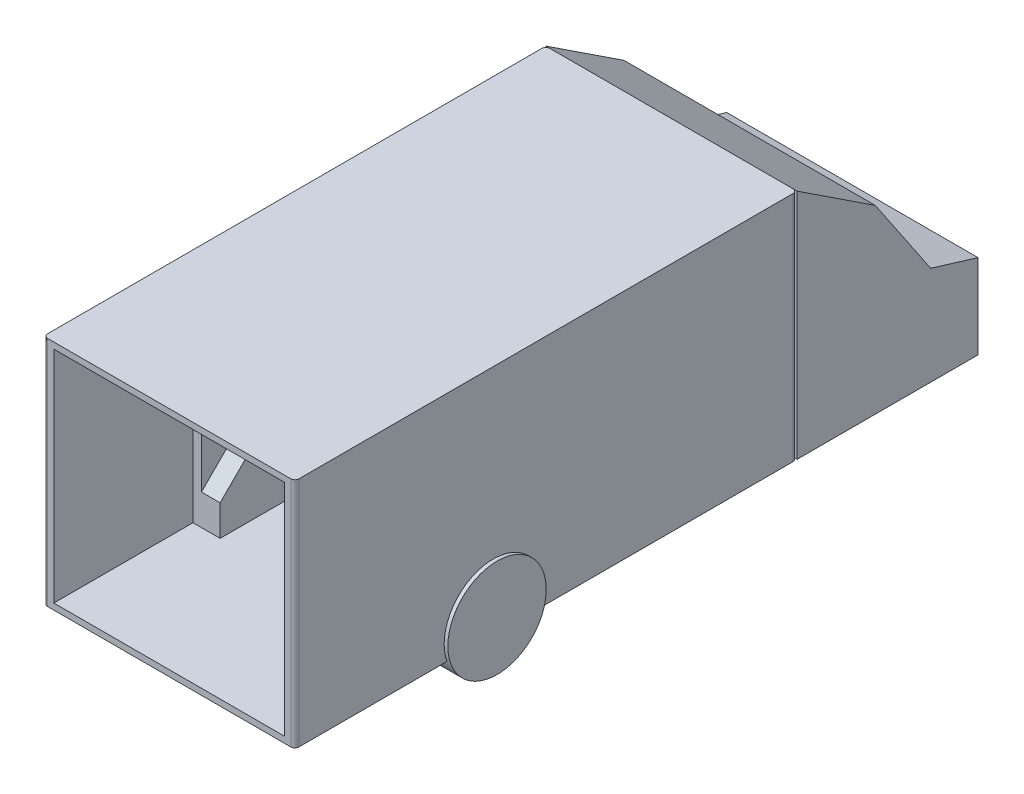
SolidWorks part; units mm, degrees
ref_plane "Front Plane" through (0, 0, 0) normal (0, 0, 1) x (1, 0, 0)
ref_plane "Top Plane" through (0, 0, 0) normal (0, 1, 0) x (1, 0, 0)
ref_plane "Right Plane" through (0, 0, 0) normal (1, 0, 0) x (0, 0, -1)
sketch "Sketch1" plane through (0, 0, 0) normal (0, 1, 0) x (1, 0, 0)
  line L0 (0, 0) -> (0, 2095.5) construction
  line L1 (-863.6, -520.7) -> (863.6, -520.7)
  line L2 (-863.6, -520.7) -> (-863.6, 520.7)
  line L3 (-863.6, 520.7) -> (863.6, 520.7)
  line L4 (863.6, -520.7) -> (863.6, 520.7)
  line L5 (-863.6, -520.7) -> (863.6, 520.7) construction
  line L6 (-863.6, 520.7) -> (863.6, -520.7) construction
  line L7 (-660.4, 520.7) -> (660.4, 520.7)
  line L8 (-660.4, 520.7) -> (-660.4, 1409.7)
  line L9 (-660.4, 1409.7) -> (660.4, 1409.7)
  line L10 (660.4, 520.7) -> (660.4, 1409.7)
  line L12 (-800.1, 1409.7) -> (800.1, 1409.7)
  line L13 (-800.1, 1409.7) -> (-800.1, 2095.5)
  line L14 (-800.1, 2095.5) -> (800.1, 2095.5)
  line L15 (800.1, 1409.7) -> (800.1, 2095.5)
  line L16 (-800.1, 2095.5) -> (723.9, 2095.5)
  line L17 (-800.1, 2095.5) -> (-800.1, 3162.3)
  line L18 (-800.1, 3162.3) -> (723.9, 3162.3)
  line L19 (723.9, 2095.5) -> (723.9, 3162.3)
  point P0 (0, 0)
  point P10 (0, 1409.7)
  point P13 (0, 2095.5)
  dimension "D1" = 1727.2
  dimension "D2" = 1041.4
  dimension "D3" = 1320.8
  dimension "D4" = 889
  dimension "D5" = 1600.2
  dimension "D6" = 685.8
  dimension "D7" = 1524
  dimension "D8" = 1066.8
sketch "Sketch2" plane through (0, 0, 0) normal (0, 1, 0) x (1, 0, 0)
  line L0 (-275, 3062.3) -> (-275, 3012.3) construction
  line L1 (-450, 3012.3) -> (-100, 3012.3)
  line L2 (-450, 3012.3) -> (-450, 2512.3)
  line L3 (-450, 2512.3) -> (-100, 2512.3)
  line L4 (-100, 3012.3) -> (-100, 2512.3)
  line L5 (-500, 3062.3) -> (-50, 3062.3)
  line L6 (-500, 3062.3) -> (-500, 2462.3)
  line L7 (-500, 2462.3) -> (-50, 2462.3)
  line L8 (-50, 3062.3) -> (-50, 2462.3)
  line L9 (-450, 2762.3) -> (-500, 2762.3) construction
  line L10 (100, 3012.3) -> (100, 2512.3)
  line L11 (100, 3012.3) -> (450, 3012.3)
  line L12 (450, 3012.3) -> (450, 2512.3)
  line L13 (100, 2512.3) -> (450, 2512.3)
  line L14 (50, 3062.3) -> (50, 2462.3)
  line L15 (50, 3062.3) -> (500, 3062.3)
  line L16 (500, 3062.3) -> (500, 2462.3)
  line L17 (50, 2462.3) -> (500, 2462.3)
  line L18 (100, 2312.3) -> (100, 1812.3)
  line L19 (100, 2312.3) -> (450, 2312.3)
  line L20 (450, 2312.3) -> (450, 1812.3)
  line L21 (100, 1812.3) -> (450, 1812.3)
  line L22 (50, 2362.3) -> (50, 1762.3)
  line L23 (50, 2362.3) -> (500, 2362.3)
  line L24 (500, 2362.3) -> (500, 1762.3)
  line L25 (50, 1762.3) -> (500, 1762.3)
  line L26 (100, 1612.3) -> (100, 1112.3)
  line L27 (100, 1612.3) -> (450, 1612.3)
  line L28 (450, 1612.3) -> (450, 1112.3)
  line L29 (100, 1112.3) -> (450, 1112.3)
  line L30 (50, 1662.3) -> (50, 1062.3)
  line L31 (50, 1662.3) -> (500, 1662.3)
  line L32 (500, 1662.3) -> (500, 1062.3)
  line L33 (50, 1062.3) -> (500, 1062.3)
  line L34 (100, 912.3) -> (100, 412.3)
  line L35 (100, 912.3) -> (450, 912.3)
  line L36 (450, 912.3) -> (450, 412.3)
  line L37 (100, 412.3) -> (450, 412.3)
  line L38 (50, 962.3) -> (50, 362.3)
  line L39 (50, 962.3) -> (500, 962.3)
  line L40 (500, 962.3) -> (500, 362.3)
  line L41 (50, 362.3) -> (500, 362.3)
  line L42 (-450, 2312.3) -> (-450, 1812.3)
  line L43 (-450, 2312.3) -> (-100, 2312.3)
  line L44 (-100, 2312.3) -> (-100, 1812.3)
  line L45 (-450, 1812.3) -> (-100, 1812.3)
  line L46 (-500, 2362.3) -> (-500, 1762.3)
  line L47 (-500, 2362.3) -> (-50, 2362.3)
  line L48 (-50, 2362.3) -> (-50, 1762.3)
  line L49 (-500, 1762.3) -> (-50, 1762.3)
  line L50 (-450, 1612.3) -> (-450, 1112.3)
  line L51 (-450, 1612.3) -> (-100, 1612.3)
  line L52 (-100, 1612.3) -> (-100, 1112.3)
  line L53 (-450, 1112.3) -> (-100, 1112.3)
  line L54 (-500, 1662.3) -> (-500, 1062.3)
  line L55 (-500, 1662.3) -> (-50, 1662.3)
  line L56 (-50, 1662.3) -> (-50, 1062.3)
  line L57 (-500, 1062.3) -> (-50, 1062.3)
  line L58 (-450, 912.3) -> (-450, 412.3)
  line L59 (-450, 912.3) -> (-100, 912.3)
  line L60 (-100, 912.3) -> (-100, 412.3)
  line L61 (-450, 412.3) -> (-100, 412.3)
  line L62 (-500, 962.3) -> (-500, 362.3)
  line L63 (-500, 962.3) -> (-50, 962.3)
  line L64 (-50, 962.3) -> (-50, 362.3)
  line L65 (-500, 362.3) -> (-50, 362.3)
  line L66 (-450, 3012.3) -> (100, 3012.3) construction
  line L67 (-450, 3012.3) -> (-450, 2312.3) construction
  line L68 (-50, 3062.3) -> (50, 3062.3) construction
  line L69 (0, 3062.3) -> (0, 2095.5) construction
  line L70 (-500, 2462.3) -> (-500, 2362.3)
  line L71 (-550, 3112.3) -> (550, 3112.3)
  line L72 (-550, 3112.3) -> (-550, 312.3)
  line L73 (-550, 312.3) -> (550, 312.3)
  line L74 (550, 3112.3) -> (550, 312.3)
  line L75 (-800.1, 3162.3) -> (723.9, 3162.3) construction
  dimension "D1" = 350
  dimension "D2" = 500
  dimension "D3" = 450
  dimension "D4" = 600
  dimension "D5" = 2
  dimension "D7" = 90
  dimension "D8" = 550
  dimension "D9" = 50
  dimension "D10" = 50
  dimension "D11" = 50
  dimension "D12" = 50
  dimension "D13" = 100
  dimension "D14" = 50
  dimension "D6" = 4
sketch "Resized Everything" plane through (0, 0, 0) normal (0, 1, 0) x (1, 0, 0)
  line L85 (-790.321, 2977.388) -> (-697.865, 2977.388)
  line L86 (-697.865, 2977.388) -> (-697.865, 3039.618)
  line L87 (-790.321, 3039.618) -> (-697.865, 3039.618)
  line L88 (-790.321, 2977.388) -> (-790.321, 3039.618)
  line L89 (-804.545, 2904.49) -> (-683.641, 2904.49)
  line L90 (-683.641, 2904.49) -> (-683.641, 2977.388)
  line L91 (-804.545, 2977.388) -> (-683.641, 2977.388)
  line L92 (-804.545, 2904.49) -> (-804.545, 2977.388)
  line L93 (-800.1, 3039.618) -> (-800.1, 3087.624)
  line L94 (-800.1, 3039.618) -> (-688.086, 3039.618)
  line L95 (-688.086, 3039.618) -> (-688.086, 3087.624)
  line L96 (-800.1, 3087.624) -> (-688.086, 3087.624)
  line L97 (-800.1, 3087.624) -> (-693.42, 3087.624)
  line L98 (-693.42, 3087.624) -> (-693.42, 3162.3)
  line L99 (-800.1, 3162.3) -> (-693.42, 3162.3)
  line L100 (-800.1, 3087.624) -> (-800.1, 3162.3)
  line L101 (-779.093, 3113.3) -> (-779.093, 3106.3)
  line L102 (-779.093, 3113.3) -> (-747.593, 3113.3)
  line L103 (-747.593, 3155.3) -> (-747.593, 3113.3)
  line L104 (-779.093, 3155.3) -> (-747.593, 3155.3)
  line L105 (-779.093, 3155.3) -> (-779.093, 3113.3)
  line L106 (-775.593, 3151.8) -> (-751.093, 3151.8)
  line L107 (-751.093, 3151.8) -> (-751.093, 3116.8)
  line L108 (-775.593, 3116.8) -> (-751.093, 3116.8)
  line L109 (-775.593, 3151.8) -> (-775.593, 3116.8)
  line L110 (-740.593, 3106.3) -> (-740.593, 3064.3)
  line L111 (-740.593, 3064.3) -> (-709.093, 3064.3)
  line L112 (-709.093, 3106.3) -> (-709.093, 3064.3)
  line L113 (-740.593, 3106.3) -> (-709.093, 3106.3)
  line L114 (-737.093, 3102.8) -> (-737.093, 3067.8)
  line L115 (-737.093, 3067.8) -> (-712.593, 3067.8)
  line L116 (-712.593, 3102.8) -> (-712.593, 3067.8)
  line L117 (-737.093, 3102.8) -> (-712.593, 3102.8)
  line L118 (-740.593, 3155.3) -> (-740.593, 3113.3)
  line L119 (-740.593, 3113.3) -> (-709.093, 3113.3)
  line L120 (-709.093, 3155.3) -> (-709.093, 3113.3)
  line L121 (-740.593, 3155.3) -> (-709.093, 3155.3)
  line L122 (-737.093, 3151.8) -> (-737.093, 3116.8)
  line L123 (-737.093, 3151.8) -> (-712.593, 3151.8)
  line L124 (-712.593, 3151.8) -> (-712.593, 3116.8)
  line L125 (-737.093, 3116.8) -> (-712.593, 3116.8)
  line L126 (-740.593, 3008.3) -> (-740.593, 2966.3)
  line L127 (-740.593, 2966.3) -> (-709.093, 2966.3)
  line L128 (-709.093, 3008.3) -> (-709.093, 2966.3)
  line L129 (-740.593, 3008.3) -> (-709.093, 3008.3)
  line L130 (-737.093, 3004.8) -> (-737.093, 2969.8)
  line L131 (-737.093, 2969.8) -> (-712.593, 2969.8)
  line L132 (-712.593, 3004.8) -> (-712.593, 2969.8)
  line L133 (-737.093, 3004.8) -> (-712.593, 3004.8)
  line L134 (-740.593, 3057.3) -> (-740.593, 3015.3)
  line L135 (-740.593, 3015.3) -> (-709.093, 3015.3)
  line L136 (-709.093, 3057.3) -> (-709.093, 3015.3)
  line L137 (-740.593, 3057.3) -> (-709.093, 3057.3)
  line L138 (-737.093, 3053.8) -> (-737.093, 3018.8)
  line L139 (-737.093, 3053.8) -> (-712.593, 3053.8)
  line L140 (-712.593, 3053.8) -> (-712.593, 3018.8)
  line L141 (-737.093, 3018.8) -> (-712.593, 3018.8)
  line L142 (-779.093, 3057.3) -> (-779.093, 3015.3)
  line L143 (-779.093, 3015.3) -> (-747.593, 3015.3)
  line L144 (-747.593, 3057.3) -> (-747.593, 3015.3)
  line L145 (-779.093, 3057.3) -> (-747.593, 3057.3)
  line L146 (-775.593, 3053.8) -> (-775.593, 3018.8)
  line L147 (-775.593, 3018.8) -> (-751.093, 3018.8)
  line L148 (-751.093, 3053.8) -> (-751.093, 3018.8)
  line L149 (-775.593, 3053.8) -> (-751.093, 3053.8)
  line L150 (-779.093, 3106.3) -> (-779.093, 3064.3)
  line L151 (-779.093, 3064.3) -> (-747.593, 3064.3)
  line L152 (-747.593, 3106.3) -> (-747.593, 3064.3)
  line L153 (-779.093, 3106.3) -> (-747.593, 3106.3)
  line L154 (-775.593, 3102.8) -> (-775.593, 3067.8)
  line L155 (-775.593, 3102.8) -> (-751.093, 3102.8)
  line L156 (-751.093, 3102.8) -> (-751.093, 3067.8)
  line L157 (-775.593, 3067.8) -> (-751.093, 3067.8)
  line L158 (-782.593, 3158.8) -> (-705.593, 3158.8)
  line L159 (-705.593, 3158.8) -> (-705.593, 2962.8)
  line L160 (-782.593, 2962.8) -> (-705.593, 2962.8)
  line L161 (-782.593, 3158.8) -> (-782.593, 2962.8)
  line L162 (-779.093, 3008.3) -> (-779.093, 2966.3)
  line L163 (-779.093, 2966.3) -> (-747.593, 2966.3)
  line L164 (-747.593, 3008.3) -> (-747.593, 2966.3)
  line L165 (-779.093, 3008.3) -> (-747.593, 3008.3)
  line L166 (-775.593, 3004.8) -> (-775.593, 2969.8)
  line L167 (-775.593, 3004.8) -> (-751.093, 3004.8)
  line L168 (-751.093, 3004.8) -> (-751.093, 2969.8)
  line L169 (-775.593, 2969.8) -> (-751.093, 2969.8)
sketch "Sketch6" plane through (0, 0, 0) normal (0, 1, 0) x (1, 0, 0)
  line L0 (-800.1, 3162.3) -> (723.9, 3162.3) construction
  line L1 (-748.0935, 2917.905) -> (-748.0935, 3167.3) construction
  line L2 (-809.2275, 2917.905) -> (-686.9595, 2917.905)
  line L3 (-686.9595, 2917.905) -> (-686.9595, 3167.3)
  line L4 (-686.9595, 3167.3) -> (-809.2275, 3167.3)
  line L5 (-696.087, 3048.381) -> (-696.087, 2990.596)
  line L6 (-800.1, 3048.381) -> (-800.1, 2990.596)
  line L7 (-809.2275, 2917.905) -> (-809.2275, 3167.3)
  line L8 (-701.04, 3162.3) -> (-696.087, 3162.3)
  line L9 (-696.087, 3162.3) -> (-696.087, 3092.958)
  line L10 (-804.2275, 2922.905) -> (-809.2275, 2922.905)
  line L11 (-691.9595, 2922.905) -> (-686.9595, 2922.905)
  line L16 (-791.0195, 2990.596) -> (-705.1675, 2990.596)
  line L17 (-705.1675, 2990.596) -> (-705.1675, 3048.381)
  line L18 (-791.0195, 3048.381) -> (-705.1675, 3048.381)
  line L19 (-791.0195, 2990.596) -> (-791.0195, 3048.381)
  line L20 (-804.2275, 2922.905) -> (-691.9595, 2922.905)
  line L21 (-691.9595, 2922.905) -> (-691.9595, 2990.596)
  line L22 (-804.2275, 2990.596) -> (-691.9595, 2990.596)
  line L23 (-804.2275, 2922.905) -> (-804.2275, 2990.596)
  line L24 (-800.1, 3048.381) -> (-800.1, 3092.958)
  line L25 (-800.1, 3048.381) -> (-696.087, 3048.381)
  line L26 (-696.087, 3048.381) -> (-696.087, 3092.958)
  line L27 (-800.1, 3092.958) -> (-696.087, 3092.958)
  line L28 (-800.1, 3092.958) -> (-701.04, 3092.958)
  line L29 (-701.04, 3092.958) -> (-701.04, 3162.3)
  line L30 (-800.1, 3162.3) -> (-701.04, 3162.3)
  line L31 (-800.1, 3092.958) -> (-800.1, 3162.3)
  point P3 (-748.0935, 2922.905)
  dimension "D1" = 239.395
  dimension "D2" = 5
  dimension "D3" = 5
  dimension "D4" = 5
extrude "Boss-Extrude1" add sketch "Sketch6" along normal blind 107 contours L2 L1 L20 L23 L22 L6 L24 L31 L30 L4 L7 | L1 L2 L3 L4 L30 L29 L27 L26 L5 L22 L21 L20 | L29 L27 L9 L8 region at (-801.3852, 0, -3070.3406) region at (-694.8018, 0, -3070.3406) region at (-698.5635, 0, -3127.629)
sketch "Sketch7" plane through (0, 0, 0) normal (0, -1, 0) x (1, 0, 0)
  line L0 (-800.1, -3048.381) -> (-800.1, -2990.596) construction
  line L1 (-696.087, -3048.381) -> (-696.087, -2990.596) construction
  line L2 (-800.1, -3048.381) -> (-800.1, -3092.958) construction
  line L3 (-800.1, -3092.958) -> (-696.087, -3092.958) construction
  line L4 (-800.1, -3092.958) -> (-701.04, -3092.958) construction
  line L5 (-701.04, -3092.958) -> (-701.04, -3162.3) construction
  line L6 (-800.1, -3162.3) -> (-701.04, -3162.3) construction
  line L7 (-800.1, -3092.958) -> (-800.1, -3162.3) construction
  line L8 (-701.04, -3162.3) -> (-696.087, -3162.3) construction
  line L9 (-696.087, -3162.3) -> (-696.087, -3092.958) construction
  line L10 (-696.087, -3048.381) -> (-696.087, -3092.958) construction
  line L11 (-800.1, -3048.381) -> (-696.087, -3048.381) construction
  line L12 (-809.2275, -2917.905) -> (-686.9595, -2917.905) construction
  line L13 (-686.9595, -2917.905) -> (-686.9595, -3167.3) construction
  line L14 (-686.9595, -3167.3) -> (-809.2275, -3167.3) construction
  line L15 (-809.2275, -2917.905) -> (-809.2275, -3167.3) construction
  line L16 (-804.2275, -2922.905) -> (-691.9595, -2922.905) construction
  line L17 (-691.9595, -2922.905) -> (-691.9595, -2990.596) construction
  line L18 (-804.2275, -2990.596) -> (-691.9595, -2990.596) construction
  line L19 (-804.2275, -2922.905) -> (-804.2275, -2990.596) construction
  line L20 (-705.1675, -2990.596) -> (-705.1675, -3048.381) construction
  line L21 (-791.0195, -3048.381) -> (-705.1675, -3048.381) construction
  line L22 (-791.0195, -2990.596) -> (-791.0195, -3048.381) construction
  line L23 (-791.0195, -2990.596) -> (-705.1675, -2990.596) construction
  line L24 (-800.1, -3048.381) -> (-800.1, -2990.596)
  line L25 (-696.087, -3048.381) -> (-696.087, -2990.596)
  line L26 (-800.1, -3048.381) -> (-800.1, -3092.958)
  line L27 (-800.1, -3092.958) -> (-696.087, -3092.958)
  line L28 (-800.1, -3092.958) -> (-701.04, -3092.958)
  line L29 (-701.04, -3092.958) -> (-701.04, -3162.3)
  line L30 (-800.1, -3162.3) -> (-701.04, -3162.3)
  line L31 (-800.1, -3092.958) -> (-800.1, -3162.3)
  line L32 (-701.04, -3162.3) -> (-696.087, -3162.3)
  line L33 (-696.087, -3162.3) -> (-696.087, -3092.958)
  line L34 (-696.087, -3048.381) -> (-696.087, -3092.958)
  line L35 (-800.1, -3048.381) -> (-696.087, -3048.381)
  line L36 (-809.2275, -2917.905) -> (-686.9595, -2917.905)
  line L37 (-686.9595, -2917.905) -> (-686.9595, -3167.3)
  line L38 (-686.9595, -3167.3) -> (-809.2275, -3167.3)
  line L39 (-809.2275, -2917.905) -> (-809.2275, -3167.3)
  line L40 (-804.2275, -2922.905) -> (-691.9595, -2922.905)
  line L41 (-691.9595, -2922.905) -> (-691.9595, -2990.596)
  line L42 (-804.2275, -2990.596) -> (-691.9595, -2990.596)
  line L43 (-804.2275, -2922.905) -> (-804.2275, -2990.596)
  line L44 (-705.1675, -2990.596) -> (-705.1675, -3048.381)
  line L45 (-791.0195, -3048.381) -> (-705.1675, -3048.381)
  line L46 (-791.0195, -2990.596) -> (-791.0195, -3048.381)
  line L47 (-791.0195, -2990.596) -> (-705.1675, -2990.596)
extrude "Boss-Extrude2" add sketch "Sketch7" along normal blind 3 contours L39 L38 L37 L36
sketch "Sketch8" plane through (0, 0, 0) normal (0, 1, 0) x (1, 0, 0)
  line L0 (-691.9595, 2922.905) -> (-686.9595, 2922.905) construction
  line L1 (-804.2275, 2922.905) -> (-809.2275, 2922.905) construction
  line L2 (-800.1, 3048.381) -> (-800.1, 2990.596) construction
  line L3 (-696.087, 3048.381) -> (-696.087, 2990.596) construction
  line L4 (-800.1, 3048.381) -> (-800.1, 3092.958) construction
  line L5 (-800.1, 3092.958) -> (-696.087, 3092.958) construction
  line L6 (-800.1, 3092.958) -> (-701.04, 3092.958) construction
  line L7 (-701.04, 3092.958) -> (-701.04, 3162.3) construction
  line L8 (-800.1, 3162.3) -> (-701.04, 3162.3) construction
  line L9 (-800.1, 3092.958) -> (-800.1, 3162.3) construction
  line L10 (-804.2275, 2922.905) -> (-691.9595, 2922.905) construction
  line L11 (-691.9595, 2922.905) -> (-691.9595, 2990.596) construction
  line L12 (-804.2275, 2990.596) -> (-691.9595, 2990.596) construction
  line L13 (-804.2275, 2922.905) -> (-804.2275, 2990.596) construction
  line L14 (-701.04, 3162.3) -> (-696.087, 3162.3) construction
  line L15 (-696.087, 3162.3) -> (-696.087, 3092.958) construction
  line L16 (-696.087, 3048.381) -> (-696.087, 3092.958) construction
  line L17 (-800.1, 3048.381) -> (-696.087, 3048.381) construction
  line L18 (-809.2275, 2917.905) -> (-686.9595, 2917.905) construction
  line L19 (-686.9595, 2917.905) -> (-686.9595, 3167.3) construction
  line L20 (-686.9595, 3167.3) -> (-809.2275, 3167.3) construction
  line L21 (-809.2275, 2917.905) -> (-809.2275, 3167.3) construction
  line L22 (-705.1675, 2990.596) -> (-705.1675, 3048.381) construction
  line L23 (-791.0195, 3048.381) -> (-705.1675, 3048.381) construction
  line L24 (-791.0195, 2990.596) -> (-791.0195, 3048.381) construction
  line L25 (-791.0195, 2990.596) -> (-705.1675, 2990.596) construction
  line L26 (-691.9595, 2922.905) -> (-686.9595, 2922.905)
  line L27 (-804.2275, 2922.905) -> (-809.2275, 2922.905)
  line L28 (-800.1, 3048.381) -> (-800.1, 2990.596)
  line L29 (-696.087, 3048.381) -> (-696.087, 2990.596)
  line L30 (-800.1, 3048.381) -> (-800.1, 3092.958)
  line L31 (-800.1, 3092.958) -> (-696.087, 3092.958)
  line L32 (-800.1, 3092.958) -> (-701.04, 3092.958)
  line L33 (-701.04, 3092.958) -> (-701.04, 3162.3)
  line L34 (-800.1, 3162.3) -> (-701.04, 3162.3)
  line L35 (-800.1, 3092.958) -> (-800.1, 3162.3)
  line L36 (-804.2275, 2922.905) -> (-691.9595, 2922.905)
  line L37 (-691.9595, 2922.905) -> (-691.9595, 2990.596)
  line L38 (-804.2275, 2990.596) -> (-691.9595, 2990.596)
  line L39 (-804.2275, 2922.905) -> (-804.2275, 2990.596)
  line L40 (-701.04, 3162.3) -> (-696.087, 3162.3)
  line L41 (-696.087, 3162.3) -> (-696.087, 3092.958)
  line L42 (-696.087, 3048.381) -> (-696.087, 3092.958)
  line L43 (-800.1, 3048.381) -> (-696.087, 3048.381)
  line L44 (-809.2275, 2917.905) -> (-686.9595, 2917.905)
  line L45 (-686.9595, 2917.905) -> (-686.9595, 3167.3)
  line L46 (-686.9595, 3167.3) -> (-809.2275, 3167.3)
  line L47 (-809.2275, 2917.905) -> (-809.2275, 3167.3)
  line L48 (-705.1675, 2990.596) -> (-705.1675, 3048.381)
  line L49 (-791.0195, 3048.381) -> (-705.1675, 3048.381)
  line L50 (-791.0195, 2990.596) -> (-791.0195, 3048.381)
  line L51 (-791.0195, 2990.596) -> (-705.1675, 2990.596)
  line M17 (-696.087, 2990.596) -> (-696.087, 3092.958)
  line M21 (-800.1, 3162.3) -> (-800.1, 2990.596)
extrude "Boss-Extrude3" add sketch "Sketch8" along normal blind 30 contours L38 L50 L43 M21 | L48 L38 L43 M17 region at (-700.6273, 0, -3019.4885) region at (-795.5597, 0, -3019.4885)
ref_plane "Plane1" through (-748.0935, 0, 0) normal (1, 0, 0) x (0, 0, -1)
sketch "Sketch9" plane through (-791.0195, 0, 0) normal (1, 0, 0) x (0, 0, -1)
  line L0 (2990.596, 15) -> (3005.596, 30)
  line L1 (3019.4885, 30) -> (3019.4885, 0) construction
  line L2 (3048.381, 15) -> (3033.381, 30)
  line L4 (2990.596, 0) -> (3048.381, 0)
  line L5 (3048.381, 0) -> (3048.381, 30)
  line L6 (3048.381, 30) -> (2990.596, 30)
  line L7 (2990.596, 30) -> (2990.596, 0)
  line L8 (2990.596, 0) -> (3048.381, 0)
  line L9 (3048.381, 0) -> (3048.381, 30)
  line L10 (3048.381, 30) -> (2990.596, 30)
  line L11 (2990.596, 30) -> (2990.596, 0)
  line M8 (3048.381, 0) -> (3048.381, 30)
  line M9 (3048.381, 30) -> (2990.596, 30)
  line M10 (2990.596, 30) -> (2990.596, 0)
  dimension "D2" = 45
  dimension "D1" = 0
extrude "Cut-Extrude1" cut sketch "Sketch9" against normal up to surface (9.0805 mm away) contours L0 M10 M9 | L2 M8 M9 region at (-791.0195, 25, -2995.596) region at (-791.0195, 25, -3043.381) up to face at (-800.1, 45.6667, -3067.0923)
sketch "Sketch10" plane through (-705.1675, 0, 0) normal (-1, 0, 0) x (0, 0, 1)
  line L0 (-3048.381, 15) -> (-3033.381, 30) construction
  line L1 (-2990.596, 15) -> (-3005.596, 30) construction
  line L2 (-3048.381, 15) -> (-3033.381, 30)
  line L3 (-2990.596, 15) -> (-3005.596, 30)
  line L4 (-3048.381, 0) -> (-2990.596, 0)
  line L5 (-3048.381, 30) -> (-3048.381, 0)
  line L6 (-2990.596, 30) -> (-3048.381, 30)
  line L7 (-2990.596, 0) -> (-2990.596, 30)
  line L8 (-3048.381, 0) -> (-2990.596, 0)
  line L9 (-3048.381, 30) -> (-3048.381, 0)
  line L10 (-2990.596, 30) -> (-3048.381, 30)
  line L11 (-2990.596, 0) -> (-2990.596, 30)
  line M6 (-2990.596, 0) -> (-2990.596, 30)
  line M7 (-2990.596, 30) -> (-3048.381, 30)
  line M8 (-3048.381, 30) -> (-3048.381, 0)
  dimension "D1" = 0
extrude "Cut-Extrude2" cut sketch "Sketch10" against normal up to surface (9.0805 mm away) contours L2 M8 M7 | L3 M6 M7 region at (-705.1675, 25, -3043.381) region at (-705.1675, 25, -2995.596) up to face at (-696.087, 45.6667, -3043.9783)
fillet "Fillet1" radius 2 8 edges at (-686.9595, 53.5, -2922.905) (-686.9595, 52, -3167.3) (-809.2275, 52, -3167.3) (-809.2275, 53.5, -2922.905) (-700.6272, 30, -3033.381) (-700.6272, 30, -3005.596) (-795.5598, 30, -3033.381) (-795.5598, 30, -3005.596) tangent propagation no
sketch "Sketch11" plane through (0, 0, 0) normal (0, 1, 0) x (-1, 0, 0)
  line L0 (804.2275, -2922.905) -> (691.9595, -2922.905)
  line L18 (791.0195, -3048.381) -> (791.0195, -2990.596)
  line L19 (791.0195, -2990.596) -> (804.2275, -2990.596)
  line L20 (804.2275, -2990.596) -> (804.2275, -2922.905)
  line L21 (804.2275, -2922.905) -> (807.2275, -2922.905)
  line L22 (809.2275, -2924.905) -> (809.2275, -2917.905)
  line L23 (809.2275, -2917.905) -> (686.9595, -2917.905)
  line L24 (686.9595, -2917.905) -> (686.9595, -2924.905)
  line L25 (688.9595, -2922.905) -> (691.9595, -2922.905)
  line L26 (691.9595, -2922.905) -> (691.9595, -2990.596)
  line L27 (691.9595, -2990.596) -> (705.1675, -2990.596)
  line L28 (705.1675, -2990.596) -> (705.1675, -3048.381)
  line L29 (705.1675, -3048.381) -> (696.087, -3048.381)
  line L30 (696.087, -3048.381) -> (696.087, -3092.958)
  line L31 (696.087, -3092.958) -> (701.04, -3092.958)
  line L32 (701.04, -3092.958) -> (701.04, -3162.3)
  line L33 (701.04, -3162.3) -> (800.1, -3162.3)
  line L34 (800.1, -3162.3) -> (800.1, -3048.381)
  line L35 (800.1, -3048.381) -> (791.0195, -3048.381)
  line L36 (791.0195, -3048.381) -> (791.0195, -2990.596)
  line L37 (791.0195, -2990.596) -> (804.2275, -2990.596)
  line L38 (804.2275, -2990.596) -> (804.2275, -2922.905)
  line L39 (804.2275, -2922.905) -> (807.2275, -2922.905)
  line L40 (809.2275, -2924.905) -> (809.2275, -2917.905)
  line L41 (809.2275, -2917.905) -> (686.9595, -2917.905)
  line L42 (686.9595, -2917.905) -> (686.9595, -2924.905)
  line L43 (688.9595, -2922.905) -> (691.9595, -2922.905)
  line L44 (691.9595, -2922.905) -> (691.9595, -2990.596)
  line L45 (691.9595, -2990.596) -> (705.1675, -2990.596)
  line L46 (705.1675, -2990.596) -> (705.1675, -3048.381)
  line L47 (705.1675, -3048.381) -> (696.087, -3048.381)
  line L48 (696.087, -3048.381) -> (696.087, -3092.958)
  line L49 (696.087, -3092.958) -> (701.04, -3092.958)
  line L50 (701.04, -3092.958) -> (701.04, -3162.3)
  line L51 (701.04, -3162.3) -> (800.1, -3162.3)
  line L52 (800.1, -3162.3) -> (800.1, -3048.381)
  line L53 (800.1, -3048.381) -> (791.0195, -3048.381)
  arc A2 (809.2275, -2924.905) -> (807.2275, -2922.905) centre (807.2275, -2924.905) ccw
  arc A3 (688.9595, -2922.905) -> (686.9595, -2924.905) centre (688.9595, -2924.905) ccw
  arc A4 (809.2275, -2924.905) -> (807.2275, -2922.905) centre (807.2275, -2924.905) ccw
  arc A5 (688.9595, -2922.905) -> (686.9595, -2924.905) centre (688.9595, -2924.905) ccw
  line M24 (804.2275, -2922.905) -> (807.2275, -2922.905)
  arc M25 (807.2275, -2922.905) -> (809.2275, -2924.905) centre (807.2275, -2924.905) cw
  line M26 (809.2275, -2924.905) -> (809.2275, -2917.905)
  line M27 (809.2275, -2917.905) -> (686.9595, -2917.905)
  line M28 (686.9595, -2917.905) -> (686.9595, -2924.905)
  arc M29 (686.9595, -2924.905) -> (688.9595, -2922.905) centre (688.9595, -2924.905) cw
  line M30 (688.9595, -2922.905) -> (691.9595, -2922.905)
  dimension "D1" = 0
extrude "Cut-Extrude3" cut sketch "Sketch11" against normal through all contours L0 M24 M25 M26 M27 M28 M29 M30 region at (-748.0935, 0, -2920.4133)
sketch "Sketch12" plane through (0, 107, 0) normal (0, 1, 0) x (1, 0, 0)
  line L0 (-804.2275, 2922.905) -> (-691.9595, 2922.905)
  line L14 (-691.9595, 2922.905) -> (-688.9595, 2922.905)
  line L15 (-686.9595, 2924.905) -> (-686.9595, 3165.3)
  line L16 (-688.9595, 3167.3) -> (-807.2275, 3167.3)
  line L17 (-809.2275, 3165.3) -> (-809.2275, 2924.905)
  line L18 (-807.2275, 2922.905) -> (-804.2275, 2922.905)
  line L19 (-804.2275, 2922.905) -> (-804.2275, 2990.596)
  line L20 (-804.2275, 2990.596) -> (-800.1, 2990.596)
  line L21 (-800.1, 2990.596) -> (-800.1, 3162.3)
  line L22 (-800.1, 3162.3) -> (-701.04, 3162.3)
  line L23 (-701.04, 3162.3) -> (-701.04, 3092.958)
  line L24 (-701.04, 3092.958) -> (-696.087, 3092.958)
  line L25 (-696.087, 3092.958) -> (-696.087, 2990.596)
  line L26 (-696.087, 2990.596) -> (-691.9595, 2990.596)
  line L27 (-691.9595, 2990.596) -> (-691.9595, 2922.905)
  line L28 (-691.9595, 2922.905) -> (-688.9595, 2922.905)
  line L29 (-686.9595, 2924.905) -> (-686.9595, 3165.3)
  line L30 (-688.9595, 3167.3) -> (-807.2275, 3167.3)
  line L31 (-809.2275, 3165.3) -> (-809.2275, 2924.905)
  line L32 (-807.2275, 2922.905) -> (-804.2275, 2922.905)
  line L33 (-804.2275, 2922.905) -> (-804.2275, 2990.596)
  line L34 (-804.2275, 2990.596) -> (-800.1, 2990.596)
  line L35 (-800.1, 2990.596) -> (-800.1, 3162.3)
  line L36 (-800.1, 3162.3) -> (-701.04, 3162.3)
  line L37 (-701.04, 3162.3) -> (-701.04, 3092.958)
  line L38 (-701.04, 3092.958) -> (-696.087, 3092.958)
  line L39 (-696.087, 3092.958) -> (-696.087, 2990.596)
  line L40 (-696.087, 2990.596) -> (-691.9595, 2990.596)
  line L41 (-691.9595, 2990.596) -> (-691.9595, 2922.905)
  arc A4 (-688.9595, 2922.905) -> (-686.9595, 2924.905) centre (-688.9595, 2924.905) ccw
  arc A5 (-686.9595, 3165.3) -> (-688.9595, 3167.3) centre (-688.9595, 3165.3) ccw
  arc A6 (-807.2275, 3167.3) -> (-809.2275, 3165.3) centre (-807.2275, 3165.3) ccw
  arc A7 (-809.2275, 2924.905) -> (-807.2275, 2922.905) centre (-807.2275, 2924.905) ccw
  arc A8 (-688.9595, 2922.905) -> (-686.9595, 2924.905) centre (-688.9595, 2924.905) ccw
  arc A9 (-686.9595, 3165.3) -> (-688.9595, 3167.3) centre (-688.9595, 3165.3) ccw
  arc A10 (-807.2275, 3167.3) -> (-809.2275, 3165.3) centre (-807.2275, 3165.3) ccw
  arc A11 (-809.2275, 2924.905) -> (-807.2275, 2922.905) centre (-807.2275, 2924.905) ccw
  line M19 (-691.9595, 2922.905) -> (-688.9595, 2922.905)
  arc M20 (-688.9595, 2922.905) -> (-686.9595, 2924.905) centre (-688.9595, 2924.905) ccw
  line M21 (-686.9595, 2924.905) -> (-686.9595, 3165.3)
  arc M22 (-686.9595, 3165.3) -> (-688.9595, 3167.3) centre (-688.9595, 3165.3) ccw
  line M23 (-688.9595, 3167.3) -> (-807.2275, 3167.3)
  arc M24 (-807.2275, 3167.3) -> (-809.2275, 3165.3) centre (-807.2275, 3165.3) ccw
  line M25 (-809.2275, 3165.3) -> (-809.2275, 2924.905)
  arc M26 (-809.2275, 2924.905) -> (-807.2275, 2922.905) centre (-807.2275, 2924.905) ccw
  line M27 (-807.2275, 2922.905) -> (-804.2275, 2922.905)
  line M28 (-804.2275, 2922.905) -> (-804.2275, 2990.596)
  line M29 (-804.2275, 2990.596) -> (-800.1, 2990.596)
  line M30 (-800.1, 2990.596) -> (-800.1, 3162.3)
  line M31 (-800.1, 3162.3) -> (-701.04, 3162.3)
  line M32 (-701.04, 3162.3) -> (-701.04, 3092.958)
  line M33 (-701.04, 3092.958) -> (-696.087, 3092.958)
  line M34 (-696.087, 3092.958) -> (-696.087, 2990.596)
  line M35 (-696.087, 2990.596) -> (-691.9595, 2990.596)
  line M36 (-691.9595, 2990.596) -> (-691.9595, 2922.905)
  dimension "D1" = 0
extrude "Boss-Extrude4" add sketch "Sketch12" along normal blind 3 separate body contours M36 M19 M20 M21 M22 M23 M24 M25 M26 M27 M28 M29 M30 M31 M32 M33 M34 M35 | L0 M28 M36 M35 M34 M33 M32 M31 M30 M29 region at (-748.7708, 107, -3039.5297) region at (-805.7275, 107, -2925.6377)
sketch "Sketch13" plane through (-705.1675, 0, 0) normal (-1, 0, 0) x (0, 0, 1)
  line L0 (-3019.4885, 30) -> (-3019.4885, 0)
  line L1 (-3048.381, 5) -> (-3019.4885, 5)
  line L6 (-3006.4244, 30) -> (-3032.5526, 30)
  line L7 (-3033.9668, 29.4142) -> (-3048.381, 15)
  line L8 (-3048.381, 15) -> (-3048.381, 0)
  line L9 (-3048.381, 0) -> (-2990.596, 0)
  line L10 (-2990.596, 0) -> (-2990.596, 15)
  line L11 (-2990.596, 15) -> (-3005.0102, 29.4142)
  line L12 (-3006.4244, 30) -> (-3032.5526, 30)
  line L13 (-3033.9668, 29.4142) -> (-3048.381, 15)
  line L14 (-3048.381, 15) -> (-3048.381, 0)
  line L15 (-3048.381, 0) -> (-2990.596, 0)
  line L16 (-2990.596, 0) -> (-2990.596, 15)
  line L17 (-2990.596, 15) -> (-3005.0102, 29.4142)
  circle A0 centre (-3019.4885, 5) radius 23.9395
  arc A2 (-3032.5526, 30) -> (-3033.9668, 29.4142) centre (-3032.5526, 28) ccw
  arc A3 (-3005.0102, 29.4142) -> (-3006.4244, 30) centre (-3006.4244, 28) ccw
  arc A4 (-3032.5526, 30) -> (-3033.9668, 29.4142) centre (-3032.5526, 28) ccw
  arc A5 (-3005.0102, 29.4142) -> (-3006.4244, 30) centre (-3006.4244, 28) ccw
  line M15 (-3048.381, 0) -> (-2990.596, 0)
  dimension "D3" = 47.879
  dimension "D2" = 10
  dimension "D1" = 0
extrude "Boss-Extrude5" add sketch "Sketch13" against normal blind 20 contours L15 A0 M15 | L1 A0 L15 L0 | L0 A0 L1 | A0 L0 M15 region at (-705.1675, 12.5181, -3008.9685) region at (-705.1675, 15.1602, -3029.6487) region at (-705.1675, 2.5092, -3031.3712) region at (-705.1675, -7.911, -3019.4885)
mirror "Mirror1" about plane through (-748.0935, 0, 0) normal (1, 0, 0) of "Boss-Extrude5"
sketch "Sketch14" plane through (-686.9595, 0, 0) normal (1, 0, 0) x (0, 0, -1)
  line L0 (3167.3, 110) -> (3167.3, 107) construction
  line L1 (3167.3, 107) -> (3167.3, -3) construction
  line L2 (3167.3, 110) -> (3167.3, 107)
  line L3 (3167.3, 107) -> (3167.3, -3)
  line L4 (3167.3, 110) -> (3205.3, 85)
  line L5 (3205.3, 85) -> (3232.3, 45)
  line L6 (3232.3, 45) -> (3255.3, 38)
  line L7 (3255.3, 38) -> (3255.3, -3)
  line L8 (3255.3, -3) -> (3167.3, -3)
  dimension "D1" = 38
  dimension "D2" = 27
  dimension "D3" = 23
  dimension "D4" = 25
  dimension "D5" = 40
  dimension "D6" = 7
extrude "Boss-Extrude6" add sketch "Sketch14" against normal up to surface (122.268 mm away) up to face at (-809.2275, 38.9899, -3036.5645)
equation "\"alpha\"= 1"
equation "\"bin_width\"= 0.5"
equation "\"bin_depth\"= 0.35"
equation "\"bin_height\"= 0.35"
